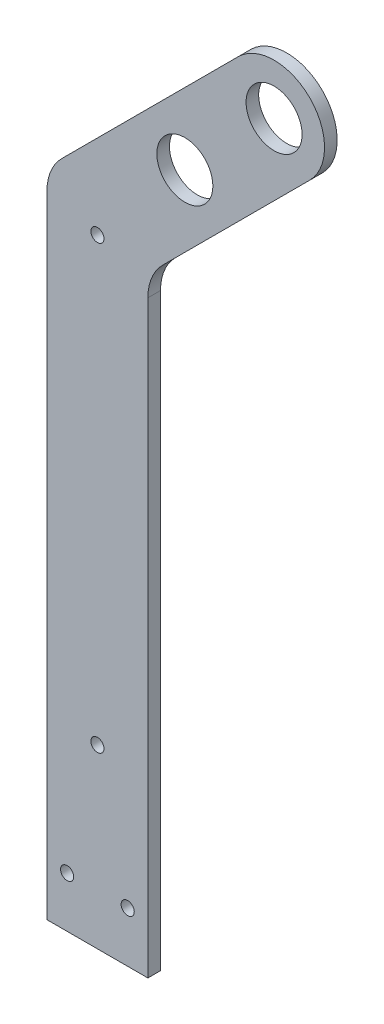
SolidWorks part; units mm, degrees
material "6061 合金"
ref_plane "前视基准面" through (0, 0, 0) normal (0, 0, 1) x (1, 0, 0)
ref_plane "上视基准面" through (0, 0, 0) normal (0, 1, 0) x (1, 0, 0)
ref_plane "右视基准面" through (0, 0, 0) normal (1, 0, 0) x (0, 0, -1)
other "Configuration Table"
sketch "草图1" plane through (0, 0, 0) normal (0, 0, 1) x (1, 0, 0)
  circle A0 centre (0, 0) radius 20
  circle A1 centre (0, 0) radius 11.1
  dimension "D1" = 40
  dimension "D2" = 22.2
extrude "凸台-拉伸1" add sketch "草图1" along normal blind 60 contours A1 | A0 region at (0, 0, 0)
ref_plane "基准面1" through (0, 0, 30) normal (0, 0, 1) x (1, 0, 0)
sketch "草图2" plane through (0, 0, 30) normal (0, 0, 1) x (1, 0, 0)
  line L0 (0, 0) -> (-70, -70) construction
  line L1 (-70, -70) -> (-70, -320) construction
  line L2 (0, -57.3148) -> (0, 49.9409) construction
  line L3 (-56.8582, 0) -> (46.4003, 0) construction
  line L4 (-14.1421, 14.1421) -> (-90, -61.7157)
  line L5 (14.1421, -14.1421) -> (-50, -78.2843)
  line L6 (-90, -61.7157) -> (-90, -320)
  line L7 (-50, -78.2843) -> (-50, -320)
  line L8 (-90, -320) -> (-50, -320)
  circle A2 centre (0, 0) radius 20 construction
  arc A3 (-14.1421, 14.1421) -> (14.1421, -14.1421) centre (0, 0) ccw
  dimension "D1" = 45
  dimension "D2" = 250
  dimension "D3" = 70
  dimension "D4" = 40
  dimension "D5" = 40
extrude "凸台-拉伸2" add sketch "草图2" along normal mid plane 60 contours L7 L8 L6 L4 A3 L5
sketch "草图4" plane through (0, 0, 60) normal (0, 0, 1) x (1, 0, 0)
  line L0 (-90, -61.7157) -> (-90, -320) construction
  line L1 (-90, -290) -> (-50, -290)
  line L2 (-90, -290) -> (-90, -350)
  line L4 (-50, -290) -> (-50, -350)
  line L5 (-50, -78.2843) -> (-50, -320) construction
  line L6 (-90, -320) -> (-50, -320) construction
  arc A0 (-90, -350) -> (-50, -350) centre (-70, -350) ccw
  circle A1 centre (-70, -350) radius 11
  dimension "D3" = 22
  dimension "D1" = 30
  dimension "D2" = 30
extrude "凸台-拉伸3" add sketch "草图4" along normal blind 5
mirror "镜向1" about plane through (0, 0, 30) normal (0, 0, 1) of "凸台-拉伸3"
sketch "草图5" plane through (0, 0, 0) normal (0, 1, 0) x (1, 0, 0)
  line L0 (0, 0) -> (0, -78.0582) construction
ref_plane "基准面2" through (-70, 0, 0) normal (-1, 0, 0) x (0, 0, 1)
sketch "草图7" plane through (-70, 0, 0) normal (-1, 0, 0) x (0, 0, 1)
  line L0 (-34.1239, -350) -> (109.535, -350) construction
sketch "草图8" plane through (0, 0, 60) normal (0, 0, 1) x (1, 0, 0)
  line L0 (0, 0) -> (-70, -70) construction
  circle A0 centre (-35.3553, -35.3553) radius 11.1
  dimension "D1" = 22.2
  dimension "D2" = 50
extrude "切除-拉伸1" cut sketch "草图8" against normal blind 100
fillet "圆角4" radius 20 2 edges at (-90, -61.7157, 30) (-50, -78.2843, 30)
fillet "圆角1" [suppressed] radius 50
fillet "圆角2" [suppressed] radius 3
sketch "草图9" plane through (0, 0, 65) normal (0, 0, 1) x (1, 0, 0)
  circle A0 centre (-70, -350) radius 13
  dimension "D1" = 26
extrude "切除-拉伸2" [suppressed] cut sketch "草图9" against normal blind 0.75
sketch "草图10" plane through (0, 0, -5) normal (0, 0, -1) x (-1, 0, 0)
  circle A0 centre (70, -350) radius 13
  dimension "D1" = 26
extrude "切除-拉伸3" [suppressed] cut sketch "草图10" against normal blind 0.75 contours A0
sketch "草图11" plane through (-90, 0, 0) normal (-1, 0, 0) x (0, 0, 1)
  circle A0 centre (48.5, -118.9949) radius 2.75
  circle A1 centre (48.5, -183.9949) radius 2.75
  circle A2 centre (48.5, -248.9949) radius 2.75
  circle A3 centre (11.5, -248.9949) radius 2.75
  circle A4 centre (11.5, -183.9949) radius 2.75
  circle A5 centre (11.5, -118.9949) radius 2.75
  dimension "D1" = 5.5
extrude "切除-拉伸4" [suppressed] cut sketch "草图11" against normal through all contours A1 | A2 | A0 | A3 | A4 | A5
sketch "草图12" [suppressed] plane through (-90, 0, 0) normal (-1, 0, 0) x (0, 0, 1)
  line L0 (30, -62.0134) -> (30, -339.6946) construction
  line L1 (10, -128.9949) -> (50, -128.9949)
  line L2 (10, -128.9949) -> (10, -173.9949)
  line L3 (10, -173.9949) -> (50, -173.9949)
  line L4 (50, -128.9949) -> (50, -173.9949)
  line L5 (10, -193.9949) -> (50, -193.9949)
  line L6 (10, -193.9949) -> (10, -238.9949)
  line L7 (10, -238.9949) -> (50, -238.9949)
  line L8 (50, -193.9949) -> (50, -238.9949)
  line L9 (10, -258.9949) -> (50, -258.9949)
  line L10 (10, -258.9949) -> (10, -290)
  line L11 (10, -290) -> (50, -290)
  line L12 (50, -258.9949) -> (50, -290)
  line L13 (19.5, -173.9949) -> (40.5, -173.9949)
  line L14 (19.5, -173.9949) -> (19.5, -193.9949)
  line L15 (19.5, -193.9949) -> (40.5, -193.9949)
  line L16 (40.5, -173.9949) -> (40.5, -193.9949)
  line L17 (19.5, -238.9949) -> (40.5, -238.9949)
  line L18 (19.5, -238.9949) -> (19.5, -258.9949)
  line L19 (19.5, -258.9949) -> (40.5, -258.9949)
  line L20 (40.5, -238.9949) -> (40.5, -258.9949)
  line L21 (60, -82.4264) -> (60, -290) construction
  line L22 (0, -290) -> (0, -82.4264) construction
  line L23 (57, -320) -> (3, -320) construction
  circle A0 centre (48.5, -118.9949) radius 2.75 construction
  circle A1 centre (48.5, -183.9949) radius 2.75 construction
  circle A2 centre (48.5, -248.9949) radius 2.75 construction
  dimension "D1" = 10
  dimension "D2" = 10
  dimension "D3" = 10
  dimension "D4" = 8
  dimension "D5" = 10
  dimension "D6" = 10
  dimension "D7" = 10
  dimension "D8" = 30
extrude "减重" [suppressed] cut sketch "草图12" against normal through all contours L0 L1 L2 L3 | L15 L0 L17 L7 L8 L5 | L0 L5 L6 L7 | L19 L0 L11 L12 L9 | L0 L9 L10 L11 | L1 L0 L13 L3 L4
fillet "圆角3" [suppressed] radius 3
sketch "草图13" plane through (0, 0, 60) normal (0, 0, 1) x (1, 0, 0)
  circle A0 centre (0, 0) radius 13
  circle A1 centre (-35.3553, -35.3553) radius 13
  dimension "D1" = 26
  dimension "D2" = 26
extrude "切除-拉伸6" [suppressed] cut sketch "草图13" against normal blind 1.75
sketch "草图14" plane through (0, 0, 0) normal (0, 0, -1) x (-1, 0, 0)
  circle A0 centre (0, 0) radius 13
  circle A1 centre (35.3553, -35.3553) radius 13
  dimension "D1" = 26
  dimension "D2" = 26
extrude "切除-拉伸7" [suppressed] cut sketch "草图14" against normal blind 1.75
sketch "草图15" [suppressed] plane through (0, 0, 0) normal (0, 0, -1) x (-1, 0, 0)
  line L0 (0, 0) -> (70, -350) construction
  line L1 (56.2719, -67.2005) -> (60.1942, -86.8121) construction
  line L2 (70, -350) -> (204.3541, -323.1292) construction
  circle A0 centre (56.2719, -67.2005) radius 2.75
  circle A1 centre (75.2172, -73.6095) radius 2.75
  circle A2 centre (60.1942, -86.8121) radius 2.75
  dimension "D1" = 5.5
  dimension "D2" = 20
  dimension "D3" = 20
  dimension "D4" = 20
  dimension "D5" = 42
  dimension "D6" = 270
extrude "切除-拉伸8" [suppressed] cut sketch "草图15" against normal through all contours A2 | A0 | A1
ref_plane "小腿主干连杆面" through (0, 0, 0) normal (0.9806, -0.1961, 0) x (0, 0, -1)
ref_plane "小腿主干对称面" through (0, 0, 30) normal (0, 0, -1) x (-1, 0, 0)
sketch "草图16" plane through (0, 0, 60) normal (0, 0, 1) x (1, 0, 0)
  line L0 (0, 0) -> (-70, -350)
  line L1 (-35.3553, -35.3553) -> (0, 0)
sketch "草图17" plane through (0, 0, 60) normal (0, 0, 1) x (1, 0, 0)
  line L0 (0, 0) -> (-70, -350) construction
  line L1 (118.6974, 32.5948) -> (32.9122, -396.3312) construction
  line L2 (92.7764, -97.0102) -> (20.2919, -82.5133)
  line L3 (73.1648, -195.0683) -> (0.6803, -180.5713)
  circle A0 centre (20.2919, -82.5133) radius 46
  circle A1 centre (0.6803, -180.5713) radius 46
  dimension "D3" = 92
  dimension "D4" = 92
  dimension "D1" = 110
  dimension "D2" = 73.92
  dimension "D5" = 180
  dimension "D6" = 280
sketch "草图18" plane through (0, 0, 60) normal (0, 0, 1) x (1, 0, 0)
  line L1 (14.1421, -14.1421) -> (-44.1421, -72.4264) construction
  line L3 (14.1421, -14.1421) -> (-44.1421, -72.4264)
  line L4 (15.4873, -12.6548) -> (52.8188, -49.9864)
  line L5 (-50, -128.5133) -> (20.2919, -128.5133)
  line L10 (-90, -290) -> (-50, -290)
  line L11 (-50, -290) -> (-50, -86.5685)
  line L12 (-44.1421, -72.4264) -> (14.1421, -14.1421)
  line L13 (-14.1421, 14.1421) -> (-84.1421, -55.8579)
  line L14 (-90, -70) -> (-90, -290)
  line L16 (-50, -128.5133) -> (-50, -86.5685)
  line L17 (-44.1421, -72.4264) -> (14.1421, -14.1421)
  circle A0 centre (20.2919, -82.5133) radius 46 construction
  arc A1 (14.1421, -14.1421) -> (-14.1421, 14.1421) centre (0, 0) ccw construction
  arc A2 (14.1421, -14.1421) -> (-14.1421, 14.1421) centre (0, 0) ccw
  arc A3 (14.1421, -14.1421) -> (15.4873, -12.6548) centre (0, 0) ccw
  arc A4 (20.2919, -128.5133) -> (52.8188, -49.9864) centre (20.2919, -82.5133) ccw
  circle A5 centre (20.2919, -82.5133) radius 35
  arc A9 (-84.1421, -55.8579) -> (-90, -70) centre (-70, -70) ccw
  arc A10 (-84.1421, -55.8579) -> (-90, -70) centre (-70, -70) ccw
  arc A11 (-44.1421, -72.4264) -> (-50, -86.5685) centre (-30, -86.5685) ccw
  arc A12 (-44.1421, -72.4264) -> (-50, -86.5685) centre (-30, -86.5685) ccw
  line M14 (-50, -290) -> (-50, -86.5685)
  line M15 (-44.1421, -72.4264) -> (14.1421, -14.1421)
  arc M16 (14.1421, -14.1421) -> (-14.1421, 14.1421) centre (0, 0) ccw
  arc M22 (-50, -86.5685) -> (-44.1421, -72.4264) centre (-30, -86.5685) cw
  dimension "D2" = 70
  dimension "D1" = 0
extrude "凸台-拉伸4" add sketch "草图18" against normal blind 5 from offset 25 contours L5 A4 L4 A5 M16 M15 M22 M14 region at (16.0508, -14.5165, 60) offset against normal yes
sketch "草图19" plane through (0, 0, 0) normal (0, 0, -1) x (-1, 0, 0)
  line L0 (50, -86.5685) -> (50, -290) construction
  line L1 (50, -134.5713) -> (50, -226.5713)
  line L2 (-0.6803, -134.5713) -> (50, -134.5713)
  line L3 (-0.6803, -226.5713) -> (50, -226.5713)
  circle A0 centre (-0.6803, -180.5713) radius 46 construction
  arc A1 (-0.6803, -134.5713) -> (-0.6803, -226.5713) centre (-0.6803, -180.5713) ccw
  circle A2 centre (-0.6803, -180.5713) radius 35
  dimension "D1" = 70
extrude "凸台-拉伸5" add sketch "草图19" against normal blind 5 from offset 25 offset against normal yes
fillet "圆角5" radius 10 2 edges at (-50, -226.5713, 27.5) (-50, -128.5133, 32.5)
sketch "草图21" plane through (0, 0, 65) normal (0, 0, 1) x (1, 0, 0)
  line L0 (-70, -350) -> (-70, -6.9331) construction
  circle A0 centre (-70, -75) radius 2.6
  circle A1 centre (-70, -250) radius 2.6
  circle A2 centre (-58, -300) radius 2.6
  circle A3 centre (-82, -300) radius 2.6
  dimension "D1" = 5.2
  dimension "D2" = 12
  dimension "D3" = 50
  dimension "D4" = 100
  dimension "D5" = 175
extrude "切除-拉伸9" cut sketch "草图21" against normal through all both and the other way through all
sketch "草图22" plane through (-90, 0, 0) normal (-1, 0, 0) x (0, 0, 1)
  line L0 (-5, -350) -> (-5, -370) construction
  line L5 (-5, -384.124) -> (5, -384.124)
  line L6 (-5, -384.124) -> (-5, 64.9179)
  line L7 (-5, 64.9179) -> (5, 64.9179)
  line L8 (5, -384.124) -> (5, 64.9179)
  line L10 (65, -370) -> (10, -370)
  line L11 (65, -370) -> (65, 61.088)
  line L12 (65, 61.088) -> (10, 61.088)
  line L13 (10, -370) -> (10, 61.088)
  dimension "D1" = 55
  dimension "D2" = 5
extrude "切除-拉伸10" cut sketch "草图22" against normal through all both contours L8 L7 L6 L5 | L13 L12 L11 L10
